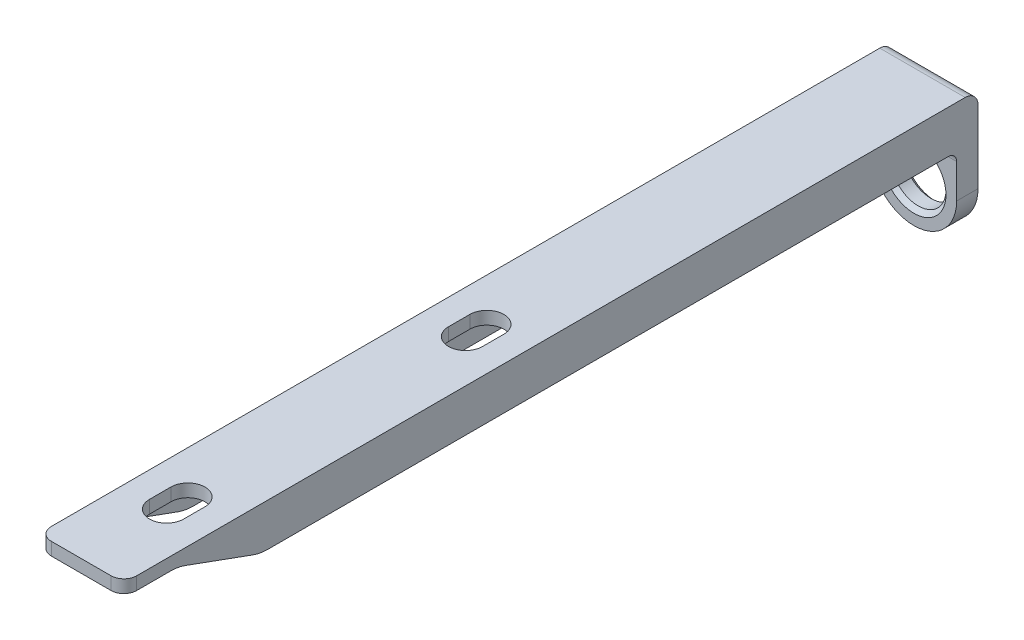
SolidWorks part; units mm, degrees
ref_plane "Front Plane" through (0, 0, 0) normal (0, 0, 1) x (1, 0, 0)
ref_plane "Top Plane" through (0, 0, 0) normal (0, 1, 0) x (1, 0, 0)
ref_plane "Right Plane" through (0, 0, 0) normal (1, 0, 0) x (0, 0, -1)
sketch "Sketch1" plane through (0, 0, 0) normal (1, 0, 0) x (0, 0, -1)
  line L0 (-159.7872, 21.7693) -> (40.2128, 21.7693)
  line L1 (40.2128, 21.7693) -> (40.2128, -8.2307)
  line L2 (40.2128, -8.2307) -> (35.2128, -8.2307)
  line L3 (35.2128, -8.2307) -> (35.2128, 18.7693)
  line L4 (35.2128, 18.7693) -> (-159.7872, 18.7693)
  line L5 (-159.7872, 18.7693) -> (-159.7872, 21.7693)
  dimension "D1" = 200
  dimension "D2" = 5
  dimension "D3" = 3
  dimension "D4" = 30
extrude "Boss-Extrude1" add sketch "Sketch1" along normal blind 20
sketch "Sketch2" plane through (0, 18.7693, 0) normal (0, -1, 0) x (1, 0, 0)
  line L0 (10, 139.7872) -> (10, 134.7872) construction
  line L1 (14, 139.7872) -> (14, 134.7872)
  line L2 (6, 139.7872) -> (6, 134.7872)
  line L3 (20, 159.7872) -> (20, -35.2128) construction
  line L4 (20, 159.7872) -> (0, 159.7872) construction
  arc A1 (14, 139.7872) -> (6, 139.7872) centre (10, 139.7872) ccw
  arc A2 (6, 134.7872) -> (14, 134.7872) centre (10, 134.7872) ccw
  point P2 (10, 137.2872)
  dimension "D1" = 4
  dimension "D2" = 10
  dimension "D3" = 20
  dimension "D4" = 5
extrude "Cut-Extrude1" cut sketch "Sketch2" against normal blind 20
pattern_linear "LPattern1" count 2 spacing 70 along (0, 0, -1) of "Cut-Extrude1"
sketch "Sketch3" plane through (0, 0, -35.2128) normal (0, 0, 1) x (1, 0, 0)
  line L0 (20, -8.2307) -> (0, -8.2307) construction
  line L1 (20, 18.7693) -> (20, -8.2307) construction
  circle A0 centre (10, 1.7693) radius 6.5
  dimension "D1" = 10
  dimension "D3" = 13
  dimension "D2" = 10
extrude "Cut-Extrude2" cut sketch "Sketch3" against normal blind 20
fillet "Fillet1" radius 3 2 edges at (10, 18.7693, -35.2128) (10, 21.7693, -40.2128)
fillet "Fillet2" radius 10 2 edges at (0, -8.2307, -37.7128) (20, -8.2307, -37.7128)
chamfer "Chamfer1" distance 1 angle 45 2 edges at (10, -4.7307, -40.2128) (16.5, 1.7693, -35.2128)
fillet "Fillet3" radius 3 2 edges at (20, 20.2693, 159.7872) (0, 20.2693, 159.7872)
sketch "Sketch4" plane through (0, 18.7693, 0) normal (0, -1, 0) x (1, 0, 0)
  line L1 (2.5, 155.3428) -> (0, 155.3428)
  line L2 (2.5, 155.3428) -> (2.5, -37.9399)
  line L3 (2.5, -37.9399) -> (0, -37.9399)
  line L4 (0, 155.3428) -> (0, -37.9399)
  dimension "D1" = 2.5
extrude "Boss-Extrude2" add sketch "Sketch4" along normal blind 7
pattern_linear "LPattern2" count 2 spacing 17.5 along (1, 0, 0) of "Boss-Extrude2"
chamfer "Chamfer2" distance 10 angle 70 2 edges at (1.25, 11.7693, 155.3428) (18.75, 11.7693, 155.3428) first distance on face at (1.25, 15.2693, 155.3428) first distance on face at (18.75, 15.2693, 155.3428)
fillet "Fillet4" radius 10 4 edges at (1.25, 18.7693, 147.1004) (18.75, 18.7693, 147.1004) (1.25, 11.7693, 127.868) (18.75, 11.7693, 127.868)
fillet "Fillet5" radius 2 2 edges at (1.25, 11.7693, -35.2128) (18.75, 11.7693, -35.2128)
